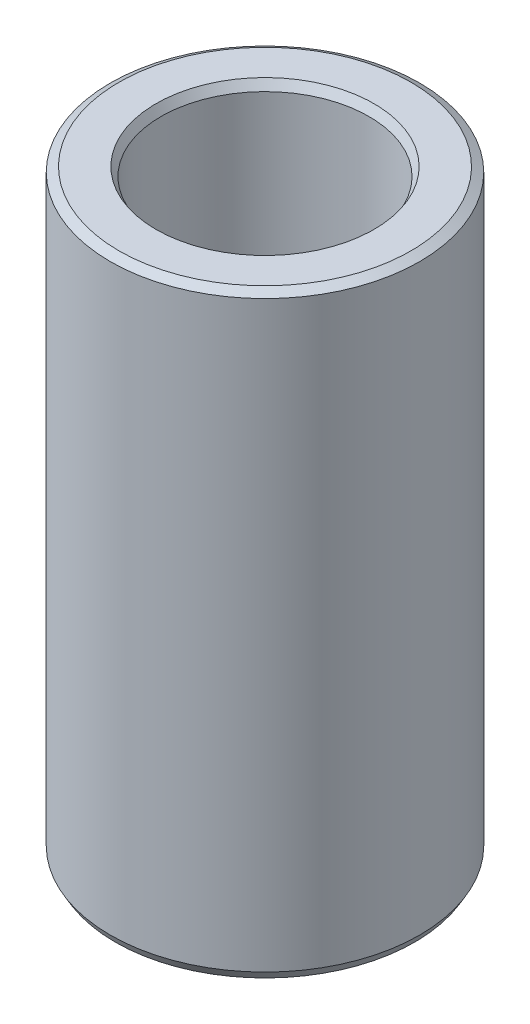
SolidWorks part; units mm, degrees
ref_plane "Front Plane" through (0, 0, 0) normal (0, 0, 1) x (1, 0, 0)
ref_plane "Top Plane" through (0, 0, 0) normal (0, 1, 0) x (1, 0, 0)
ref_plane "Right Plane" through (0, 0, 0) normal (1, 0, 0) x (0, 0, -1)
sketch "Sketch1" plane through (0, 0, 0) normal (0, 1, 0) x (1, 0, 0)
  circle A0 centre (0, 0) radius 35
  dimension "SLEEVE_OD" = 70
extrude "Boss-Extrude1" add sketch "Sketch1" along normal blind 135.0578
sketch "Sketch2" plane through (0, 0, 0) normal (0, 1, 0) x (1, 0, 0)
  circle A0 centre (0, 0) radius 23.5343
  dimension "BORE_D" = 47.0687
extrude "Cut-Extrude1" cut sketch "Sketch2" along normal through all
chamfer "Chamfer1" distance 1.1294 angle 60 4 edges at (0, 135.0578, 23.5343) (0, 0, 23.5343) (0, 0, 35) (0, 135.0578, 35) first distance on face at (0, 135.0578, 23.5343) first distance on face at (0, 0, 23.5343) first distance on face at (0, 135.0578, 35)
